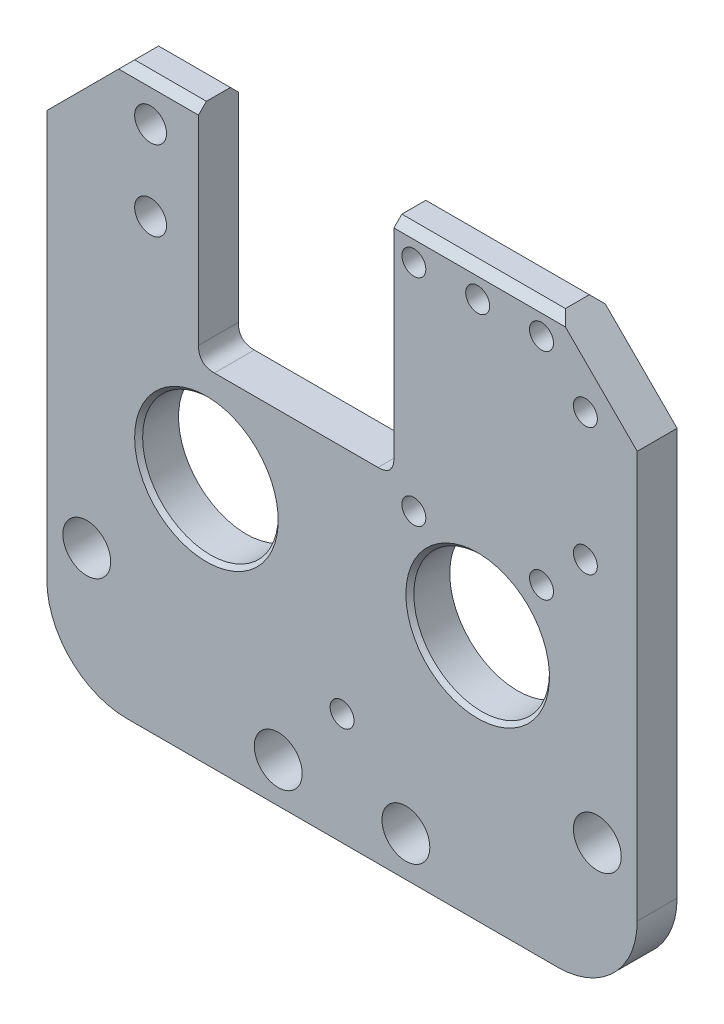
SolidWorks part; units mm, degrees
material "Stop 1060"
ref_plane "Płaszczyzna przednia" through (0, 0, 0) normal (0, 0, 1) x (1, 0, 0)
ref_plane "Płaszczyzna górna" through (0, 0, 0) normal (0, 1, 0) x (1, 0, 0)
ref_plane "Płaszczyzna prawa" through (0, 0, 0) normal (1, 0, 0) x (0, 0, -1)
sketch "Szkic1" plane through (0, 0, 0) normal (0, 0, 1) x (1, 0, 0)
  line L2 (34, 36) -> (34, -35)
  line L3 (34, -35) -> (-20, -35)
  line L6 (-20, -35) -> (-20, 36)
  line L7 (-20, 36) -> (34, 36)
  dimension "D1" = 71
  dimension "D2" = 20
  dimension "D3" = 54
  dimension "D4" = 36
extrude "Dodanie-wyciągnięcie1" add sketch "Szkic1" along normal blind 5
sketch "Szkic2" plane through (0, 0, 5) normal (0, 0, 1) x (1, 0, 0)
  line L1 (-20, 36) -> (3.5, 36)
  line L2 (-20, 36) -> (-20, 8)
  line L3 (-20, 8) -> (3.5, 8)
  line L4 (3.5, 36) -> (3.5, 8)
  dimension "D1" = 28
  dimension "D2" = 23.5
extrude "Wytnij-wyciągnięcie1" cut sketch "Szkic2" against normal blind 5
sketch "Szkic3" plane through (0, 0, 0) normal (0, 0, -1) x (-1, 0, 0)
  line L0 (-3.5, 8) -> (-3.5, 36) construction
  line L1 (-3.5, 30.5) -> (-24.5, 30.5)
  line L2 (-3.5, 30.5) -> (-3.5, 9.5)
  line L3 (-3.5, 9.5) -> (-24.5, 9.5)
  line L4 (-24.5, 30.5) -> (-24.5, 9.5)
  line L5 (-34, 36) -> (-3.5, 36) construction
  dimension "D1" = 5.5
  dimension "D2" = 21
  dimension "D3" = 21
extrude "Wytnij-wyciągnięcie2" cut sketch "Szkic3" against normal blind 3
sketch "Szkic4" plane through (0, 0, 5) normal (0, 0, 1) x (1, 0, 0)
  line L0 (3.5, 8) -> (3.5, 36) construction
  line L1 (34, 36) -> (3.5, 36) construction
  circle A0 centre (6, 32.5) radius 1.5
  circle A1 centre (14, 32.5) radius 1.5
  circle A2 centre (22, 32.5) radius 1.5
  circle A4 centre (22, 5.5) radius 1.5
  circle A5 centre (6, 5.5) radius 1.5
  circle A6 centre (27.5, 27) radius 1.5
  circle A7 centre (27.5, 11) radius 1.5
  circle A8 centre (14, 5.5) radius 1.5 [skipped]
  dimension "D1" = 2.5
  dimension "D2" = 3
  dimension "D4" = 3
  dimension "D6" = 8
  dimension "D8" = 5.5
  dimension "D10" = 3
  dimension "D3" = 3.5
  dimension "D5" = 2
  dimension "D7" = 27
  dimension "D9" = 5.5
  dimension "D11" = 2
extrude "Wytnij-wyciągnięcie3" cut sketch "Szkic4" against normal blind 5
sketch "Szkic5" plane through (0, 0, 5) normal (0, 0, 1) x (1, 0, 0)
  line L1 (-20, 8) -> (-40, 8)
  line L2 (-20, 8) -> (-20, -35)
  line L3 (-20, -35) -> (-40, -35)
  line L4 (-40, 8) -> (-40, -35)
  dimension "D1" = 20
  dimension "D2" = 43
extrude "Dodanie-wyciągnięcie2" add sketch "Szkic5" against normal blind 5
sketch "Szkic6" plane through (0, 0, 5) normal (0, 0, 1) x (1, 0, 0)
  line L0 (-40, 8) -> (-40, -35) construction
  line L1 (-40, 8) -> (3.5, 8) construction
  circle A0 centre (-20, -4) radius 8.5
  circle A1 centre (14, -4) radius 8.5
  dimension "D1" = 20
  dimension "D3" = 17
  dimension "D2" = 12
  dimension "D5" = 34
  dimension "D4" = 2
extrude "Wytnij-wyciągnięcie4" cut sketch "Szkic6" against normal blind 5
sketch "symetria" plane through (0, 0, 5) normal (0, 0, 1) x (1, 0, 0)
  line L0 (-20, -4) -> (14, -4)
  line L1 (-3, -4) -> (-3, -39)
  dimension "D1" = 35
sketch "Szkic7" plane through (0, 0, 5) normal (0, 0, 1) x (1, 0, 0)
  line L0 (-3, -4) -> (-3, -39) construction
  line L1 (-40, -35) -> (34, -35) construction
  line L2 (-3, -36.4153) -> (-3, -30)
  line L3 (-40, 8) -> (-40, -35) construction
  circle A0 centre (5, -30) radius 3
  circle A1 centre (-11, -30) radius 3
  circle A2 centre (-35, -19) radius 3
  circle A3 centre (29, -19) radius 3
  dimension "D1" = 6
  dimension "D4" = 6
  dimension "D2" = 8
  dimension "D3" = 5
  dimension "D5" = 5
  dimension "D6" = 16
extrude "Wytnij-wyciągnięcie5" cut sketch "Szkic7" against normal blind 10 contours A1 | A0 | A2 | A3 region at (5, -30, 5) region at (-11, -30, 5) region at (-35, -19, 5) region at (29, -19, 5)
fillet "Zaokrąglenie3" radius 10 2 edges at (34, -35, 2.5) (-40, -35, 2.5)
sketch "Szkic8" plane through (0, 0, 5) normal (0, 0, 1) x (1, 0, 0)
  line L1 (-40, 8) -> (-21, 8)
  line L2 (-40, 8) -> (-40, 36)
  line L3 (-40, 36) -> (-21, 36)
  line L4 (-21, 8) -> (-21, 36)
  dimension "D1" = 19
  dimension "D2" = 28
extrude "Dodanie-wyciągnięcie3" add sketch "Szkic8" against normal blind 5
fillet "Zaokrąglenie2" radius 2 2 edges at (3.5, 8, 2.5) (-21, 8, 2.5) conic rho 0.5
sketch "Szkic9" plane through (0, 0, 5) normal (0, 0, 1) x (1, 0, 0)
  line L2 (-21, 10) -> (-21, 36) construction
  line L3 (-21, 36) -> (-40, 36) construction
  circle A1 centre (-27, 31) radius 2
  circle A2 centre (-27, 21) radius 2
  dimension "D1" = 6
  dimension "D2" = 6
  dimension "D3" = 4
  dimension "D4" = 4
  dimension "D6" = 10
  dimension "D5" = 5
extrude "Wytnij-wyciągnięcie6" cut sketch "Szkic9" against normal blind 10
chamfer "Chamfer1" distance 10 angle 45 2 edges at (-40, 36, 2.5) (34, 36, 2.5)
chamfer "Sfazowanie2" distance 1 angle 45 4 edges at (13.75, 36, 5) (13.75, 36, 0) (-25.5, 36, 0) (-25.5, 36, 5)
chamfer "Sfazowanie3" distance 0.5 angle 45 2 edges at (-11.5, -4, 5) (22.5, -4, 5)
sketch "Szkic10" plane through (0, 0, 5) normal (0, 0, 1) x (1, 0, 0)
  line L0 (-3, -4) -> (-3, -39) construction
  line L1 (-30, -35) -> (24, -35) construction
  circle A0 centre (-3, -21) radius 1.5
  dimension "D1" = 14
  dimension "D2" = 3
extrude "Wytnij-wyciągnięcie7" cut sketch "Szkic10" against normal blind 10
